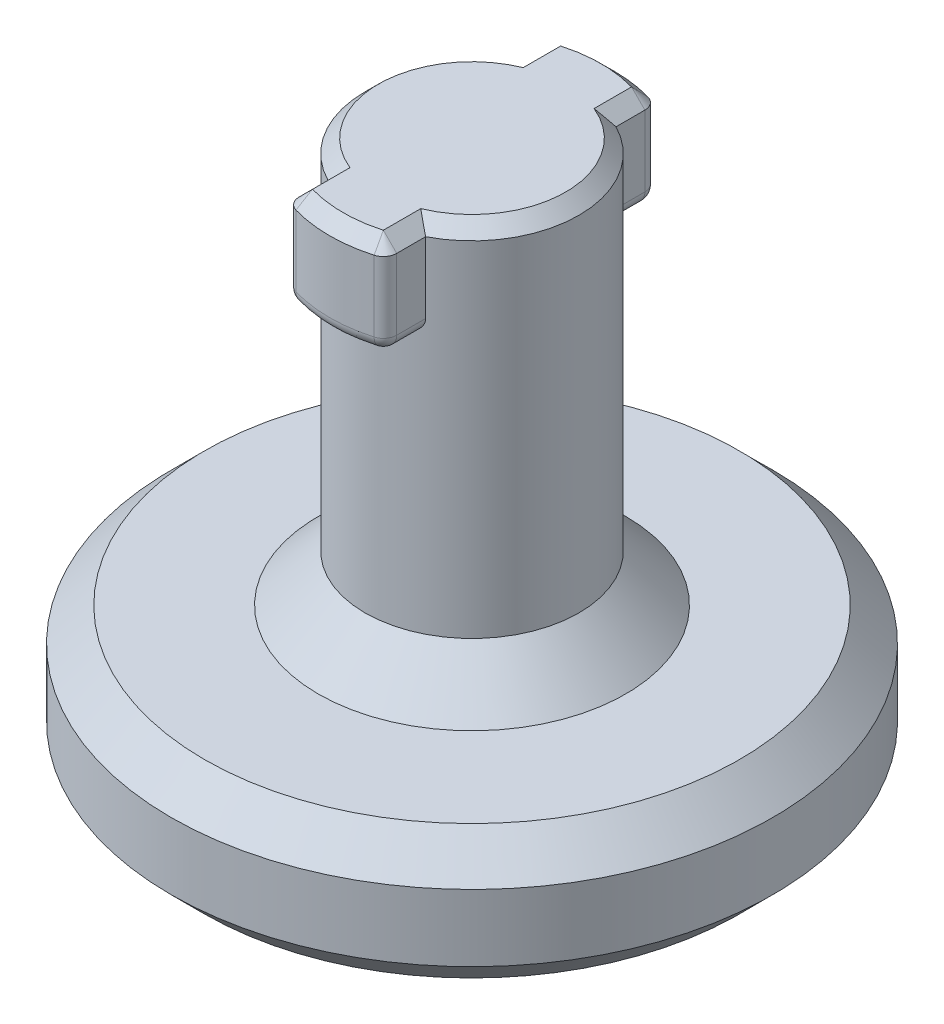
SolidWorks part; units mm, degrees
ref_plane "Front Plane" through (0, 0, 0) normal (0, 0, 1) x (1, 0, 0)
ref_plane "Top Plane" through (0, 0, 0) normal (0, 1, 0) x (1, 0, 0)
ref_plane "Right Plane" through (0, 0, 0) normal (1, 0, 0) x (0, 0, -1)
sketch "Sketch1" plane through (0, 0, 0) normal (0, 1, 0) x (1, 0, 0)
  circle A0 centre (0, 0) radius 4.5
  circle A1 centre (0, 0) radius 1.6
  dimension "D1" = 3.2
  dimension "D2" = 9
extrude "Boss-Extrude1" add sketch "Sketch1" along normal blind 2
extrude "Boss-Extrude2" add sketch "Sketch1<2>" along normal blind 8.05 contours A1 region at (0, 0, 0)
sketch "Sketch1<2>" plane through (0, 0, 0) normal (0, 1, 0) x (1, 0, 0) same geometry as "Sketch1"
chamfer "Chamfer1" distance 0.7 1 edges at (0, 2, 1.6)
chamfer "Chamfer2" distance 0.5 angle 45 2 edges at (0, 2, 4.5) (0, 0, 4.5)
sketch "Sketch2" plane through (0, 8.05, 0) normal (0, 1, 0) x (1, 0, 0)
  line L0 (-0.73, 2.001) -> (-0.73, -2.001)
  line L1 (-0.73, 2.001) -> (0.73, 2.001)
  line L2 (-0.73, -2.001) -> (0.73, -2.001)
  line L3 (0.73, 2.001) -> (0.73, -2.001)
  line L4 (-0.73, 2.001) -> (0.73, -2.001) construction
  line L5 (-0.73, -2.001) -> (0.73, 2.001) construction
  circle A0 centre (0, 0) radius 2.13
  point P1 (0, 0)
  circle M5 centre (0, 0) radius 1.6
  dimension "D1" = 4.26
  dimension "D2" = 1.46
extrude "Boss-Extrude3" add sketch "Sketch2" against normal blind 1.46 contours L1 A0 | L3 L1 L0 M5 | L3 L0 L2 M5 | L2 A0 region at (0, 8.05, -1.7688) region at (0, 8.05, -2.0527) region at (0, 8.05, 1.7688) region at (0, 8.05, 2.0527)
fillet "Fillet1" radius 0.2 10 edges at (-0.73, 7.32, 2.001) (0.73, 7.32, 2.001) (-0.73, 7.32, -2.001) (0.73, 7.32, -2.001) (0.73, 6.59, 1.7124) (0, 6.59, 2.13) (-0.73, 6.59, 1.7124) (-0.73, 6.59, -1.7124) (0, 6.59, -2.13) (0.73, 6.59, -1.7124)
chamfer "Chamfer3" [suppressed] distance 0.5 angle 45
chamfer "Chamfer4" distance 0.2 angle 45 12 edges at (-1.6, 8.05, 0) (-0.73, 8.05, -1.6398) (-0.6897, 8.05, -1.9762) (0, 8.05, -2.13) (0.6897, 8.05, -1.9762) (0.73, 8.05, -1.6398) (1.6, 8.05, 0) (0.73, 8.05, 1.6398) (0.6897, 8.05, 1.9762) (0, 8.05, 2.13) (-0.6897, 8.05, 1.9762) (-0.73, 8.05, 1.6398)
equation "\"D1@Sketch1\"=3.3-0.1"
equation "\"D2@Sketch2\"=1.5-0.04"
equation "\"D1@Sketch2\"=3.26+1"
